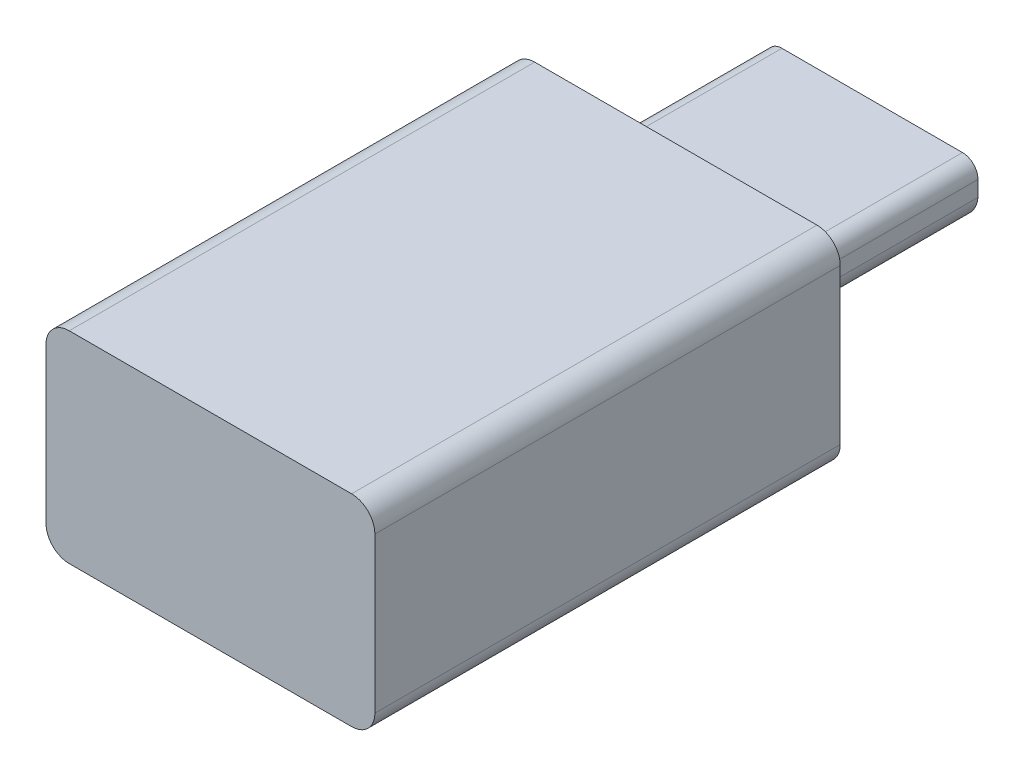
SolidWorks part; units mm, degrees
ref_plane "Front Plane" through (0, 0, 0) normal (0, 0, 1) x (1, 0, 0)
ref_plane "Top Plane" through (0, 0, 0) normal (0, 1, 0) x (1, 0, 0)
ref_plane "Right Plane" through (0, 0, 0) normal (1, 0, 0) x (0, 0, -1)
sketch "Sketch1" plane through (0, 0, 87.6019) normal (0, 0, -1) x (-1, 0, 0)
  line L1 (38.2707, 36.8406) -> (47.3707, 36.8406)
  line L2 (37.5207, 36.0906) -> (37.5207, 31.0906)
  line L3 (38.2707, 30.3406) -> (47.3707, 30.3406)
  line L4 (48.1207, 36.0906) -> (48.1207, 31.0906)
  arc A0 (37.5207, 31.0906) -> (38.2707, 30.3406) centre (38.2707, 31.0906) ccw
  arc A1 (47.3707, 30.3406) -> (48.1207, 31.0906) centre (47.3707, 31.0906) ccw
  arc A2 (47.3707, 36.8406) -> (48.1207, 36.0906) centre (47.3707, 36.0906) cw
  arc A3 (38.2707, 36.8406) -> (37.5207, 36.0906) centre (38.2707, 36.0906) ccw
  point P8 (48.1207, 30.3406)
  point P11 (48.1207, 36.8406)
  point P14 (37.5207, 36.8406)
  dimension "D3" = 0.75
  dimension "D1" = 10.6
  dimension "D2" = 6.5
extrude "Boss-Extrude1" add sketch "Sketch1" along normal blind 15
sketch "Sketch2" plane through (0, 0, 72.6019) normal (0, 0, -1) x (-1, 0, 0)
  line L0 (42.8207, 36.8406) -> (42.8207, 28.6005) construction
  line L1 (47.3707, 36.8406) -> (38.2707, 36.8406) construction
  line L2 (37.5207, 33.5906) -> (48.1207, 33.5906) construction
  line L3 (37.5207, 36.0906) -> (37.5207, 31.0906) construction
  line L4 (48.1207, 31.0906) -> (48.1207, 36.0906) construction
  line L5 (40.3207, 33.0506) -> (45.3207, 33.0506)
  line L6 (39.9107, 34.8806) -> (45.7307, 34.8806)
  line L7 (46.2307, 34.3806) -> (46.2307, 33.8806)
  line L8 (40.3207, 33.0506) -> (45.3207, 33.0506)
  line L9 (39.4107, 34.3806) -> (39.4107, 33.8806)
  arc A0 (45.3207, 33.0506) -> (46.2307, 33.8806) centre (45.3207, 33.9644) ccw
  arc A1 (45.7307, 34.8806) -> (46.2307, 34.3806) centre (45.7307, 34.3806) cw
  arc A2 (39.9107, 34.8806) -> (39.4107, 34.3806) centre (39.9107, 34.3806) ccw
  arc A3 (40.3207, 33.0506) -> (39.4107, 33.8806) centre (40.3207, 33.9644) cw
  point P10 (42.8207, 33.5906)
  point P13 (42.8207, 33.0506)
  point P15 (39.4107, 34.8806)
  point P19 (46.2307, 34.8806)
  point P26 (42.8207, 34.8806)
  dimension "D2" = 0.5
  dimension "D1" = 1
  dimension "D3" = 2.5
  dimension "D4" = 3.79
extrude "Boss-Extrude2" add sketch "Sketch2" along normal blind 6.33 contours A3 L5 A0 L7 A1 L6 A2 L9 region at (-42.8207, 33.9793, 72.6019)
ref_plane "Plane1" through (-42.8207, 0, 0) normal (1, 0, 0) x (0, 0, -1)
